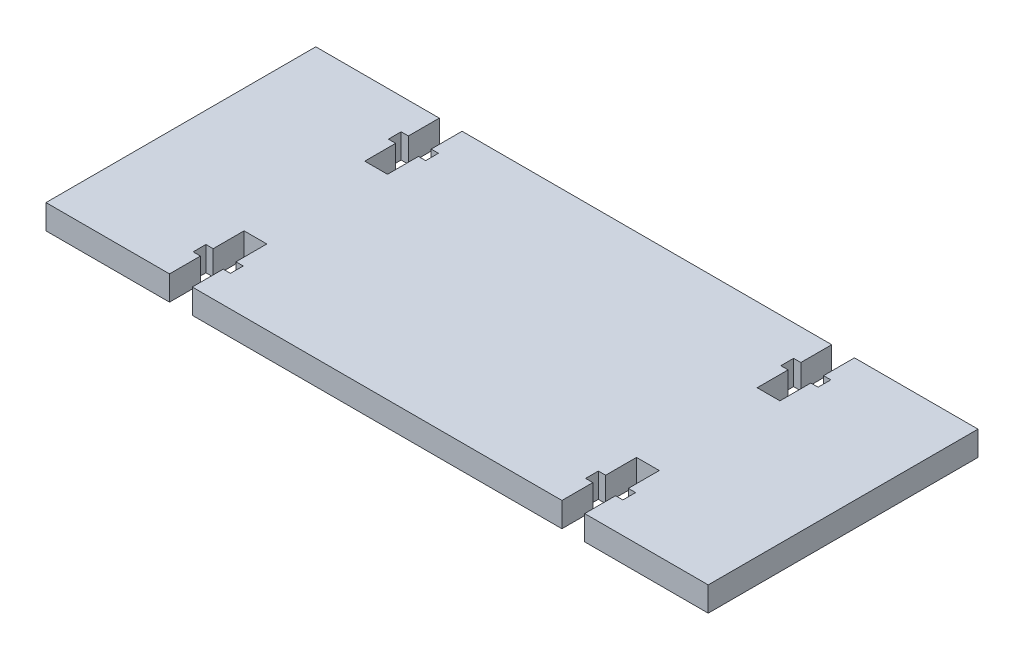
SolidWorks part; units mm, degrees
ref_plane "Front Plane" through (0, 0, 0) normal (0, 0, 1) x (1, 0, 0)
ref_plane "Top Plane" through (0, 0, 0) normal (0, 1, 0) x (1, 0, 0)
ref_plane "Right Plane" through (0, 0, 0) normal (1, 0, 0) x (0, 0, -1)
sketch "Sketch1" plane through (0, 0, 0) normal (0, 1, 0) x (1, 0, 0)
  line L1 (-42.8625, -17.4625) -> (42.8625, -17.4625)
  line L2 (-42.8625, -17.4625) -> (-42.8625, 17.4625)
  line L3 (-42.8625, 17.4625) -> (42.8625, 17.4625)
  line L4 (42.8625, -17.4625) -> (42.8625, 17.4625)
  line L5 (-42.8625, -17.4625) -> (42.8625, 17.4625) construction
  line L6 (-42.8625, 17.4625) -> (42.8625, -17.4625) construction
  point P0 (0, 0)
  dimension "D1" = 85.725
  dimension "D2" = 34.925
extrude "Boss-Extrude1" add sketch "Sketch1" along normal blind 3.175
sketch "Sketch3" plane through (0, 0, 0) normal (0, -1, 0) x (1, 0, 0)
  line L0 (-42.8625, 17.4625) -> (42.8625, 17.4625) construction
  line L1 (-26.8732, 17.4625) -> (-23.9268, 17.4625)
  line L2 (-26.8732, 17.4625) -> (-26.8732, 13.462)
  line L3 (-26.8732, 7.8105) -> (-23.9268, 7.8105)
  line L4 (-23.9268, 17.4625) -> (-23.9268, 13.462)
  line L5 (-26.8732, 17.4625) -> (-23.9268, 7.8105) construction
  line L6 (-26.8732, 13.462) -> (-27.813, 13.462)
  line L7 (-22.987, 11.811) -> (-23.9268, 11.811)
  line L8 (-22.987, 11.811) -> (-22.987, 13.462)
  line L9 (-22.987, 13.462) -> (-23.9268, 13.462)
  line L10 (-27.813, 11.811) -> (-27.813, 13.462)
  line L11 (-22.987, 11.811) -> (-27.813, 13.462) construction
  line L12 (-22.987, 13.462) -> (-27.813, 11.811) construction
  line L13 (-23.9268, 11.811) -> (-23.9268, 7.8105)
  line L14 (-26.8732, 11.811) -> (-27.813, 11.811)
  line L15 (-26.8732, 11.811) -> (-26.8732, 7.8105)
  line L16 (-25.4, 7.8105) -> (-25.4, 17.4625) construction
  line L17 (0, 17.4625) -> (0, -17.4625) construction
  line L18 (42.8625, -17.4625) -> (-42.8625, -17.4625) construction
  line L19 (25.4, 7.8105) -> (25.4, 17.4625) construction
  line L20 (22.987, 13.462) -> (27.813, 11.811) construction
  line L21 (22.987, 11.811) -> (27.813, 13.462) construction
  line L22 (26.8732, 17.4625) -> (23.9268, 7.8105) construction
  line L23 (26.8732, 11.811) -> (26.8732, 7.8105)
  line L24 (26.8732, 11.811) -> (27.813, 11.811)
  line L25 (23.9268, 11.811) -> (23.9268, 7.8105)
  line L26 (27.813, 11.811) -> (27.813, 13.462)
  line L27 (22.987, 13.462) -> (23.9268, 13.462)
  line L28 (22.987, 11.811) -> (22.987, 13.462)
  line L29 (22.987, 11.811) -> (23.9268, 11.811)
  line L30 (26.8732, 13.462) -> (27.813, 13.462)
  line L31 (23.9268, 17.4625) -> (23.9268, 13.462)
  line L32 (26.8732, 7.8105) -> (23.9268, 7.8105)
  line L33 (26.8732, 17.4625) -> (26.8732, 13.462)
  line L34 (26.8732, 17.4625) -> (23.9268, 17.4625)
  line L35 (-42.8625, 0) -> (-37.7203, 0) construction
  line L36 (-42.8625, -17.4625) -> (-42.8625, 17.4625) construction
  line L37 (26.8732, -17.4625) -> (23.9268, -7.8105) construction
  line L38 (22.987, -11.811) -> (27.813, -13.462) construction
  line L39 (22.987, -13.462) -> (27.813, -11.811) construction
  line L40 (25.4, -7.8105) -> (25.4, -17.4625) construction
  line L41 (26.8732, -17.4625) -> (23.9268, -17.4625)
  line L42 (26.8732, -17.4625) -> (26.8732, -13.462)
  line L43 (26.8732, -7.8105) -> (23.9268, -7.8105)
  line L44 (23.9268, -17.4625) -> (23.9268, -13.462)
  line L45 (26.8732, -13.462) -> (27.813, -13.462)
  line L46 (22.987, -11.811) -> (23.9268, -11.811)
  line L47 (22.987, -11.811) -> (22.987, -13.462)
  line L48 (22.987, -13.462) -> (23.9268, -13.462)
  line L49 (27.813, -11.811) -> (27.813, -13.462)
  line L50 (23.9268, -11.811) -> (23.9268, -7.8105)
  line L51 (26.8732, -11.811) -> (27.813, -11.811)
  line L52 (26.8732, -11.811) -> (26.8732, -7.8105)
  line L53 (-25.4, -7.8105) -> (-25.4, -17.4625) construction
  line L54 (-22.987, -13.462) -> (-27.813, -11.811) construction
  line L55 (-22.987, -11.811) -> (-27.813, -13.462) construction
  line L56 (-26.8732, -17.4625) -> (-23.9268, -7.8105) construction
  line L57 (-26.8732, -11.811) -> (-26.8732, -7.8105)
  line L58 (-26.8732, -11.811) -> (-27.813, -11.811)
  line L59 (-23.9268, -11.811) -> (-23.9268, -7.8105)
  line L60 (-27.813, -11.811) -> (-27.813, -13.462)
  line L61 (-22.987, -13.462) -> (-23.9268, -13.462)
  line L62 (-22.987, -11.811) -> (-22.987, -13.462)
  line L63 (-22.987, -11.811) -> (-23.9268, -11.811)
  line L64 (-26.8732, -13.462) -> (-27.813, -13.462)
  line L65 (-23.9268, -17.4625) -> (-23.9268, -13.462)
  line L66 (-26.8732, -7.8105) -> (-23.9268, -7.8105)
  line L67 (-26.8732, -17.4625) -> (-26.8732, -13.462)
  line L68 (-26.8732, -17.4625) -> (-23.9268, -17.4625)
  point P6 (-25.4, 12.6365)
  point P18 (-25.4, 12.6365)
  point P36 (25.4, 12.6365)
  point P56 (25.4, -12.6365)
  point P71 (-25.4, -12.6365)
  dimension "D1" = 9.652
  dimension "D2" = 2.9464
  dimension "D3" = 1.651
  dimension "D4" = 4.826
  dimension "D5" = 25.4
extrude "Cut-Extrude2" cut sketch "Sketch3" against normal through all
